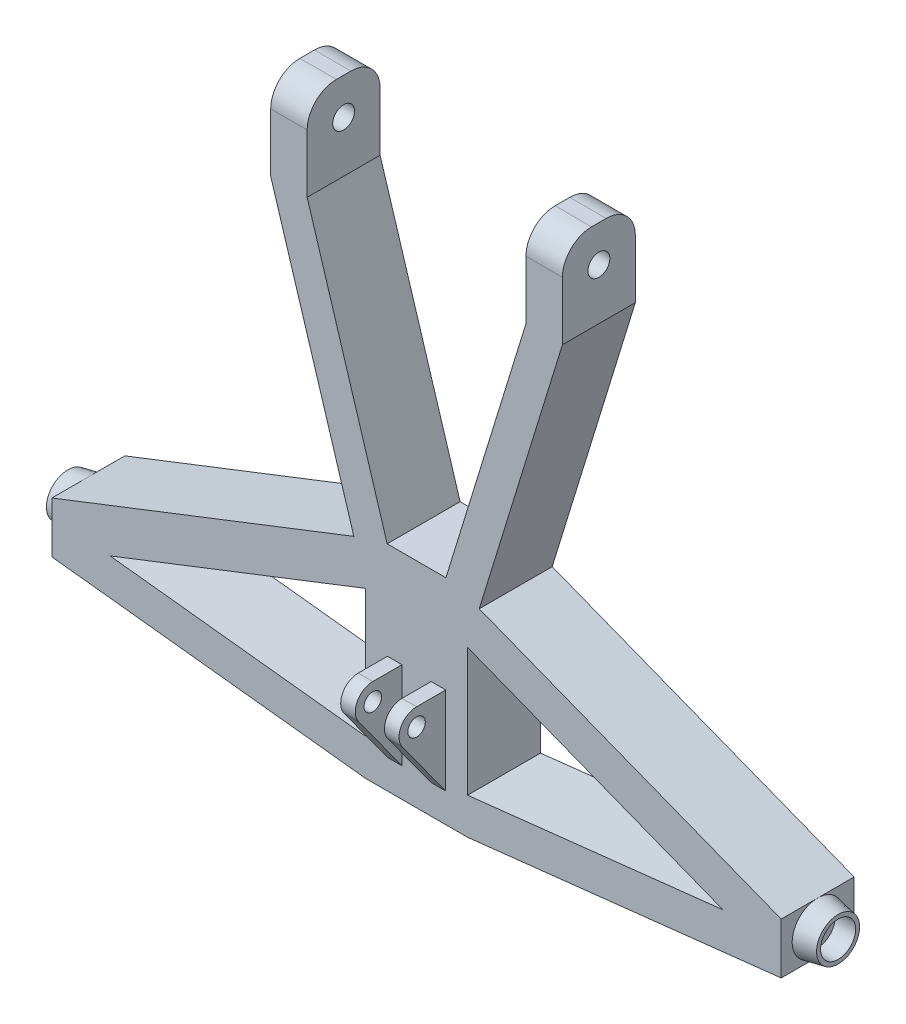
SolidWorks part; units mm, degrees
material "1060-H14"
ref_plane "Front Plane" through (0, 0, 0) normal (0, 0, 1) x (1, 0, 0)
ref_plane "Top Plane" through (0, 0, 0) normal (0, 1, 0) x (1, 0, 0)
ref_plane "Right Plane" through (0, 0, 0) normal (1, 0, 0) x (0, 0, -1)
sketch "Sketch1" plane through (0, 0, 0) normal (0, 0, 1) x (1, 0, 0)
  line L0 (100, 238.2726) -> (75, 238.2726)
  line L1 (-75, 238.2726) -> (-75, 178.2726)
  line L2 (-75, 178.2726) -> (0, -65.4485)
  line L3 (100, 178.2726) -> (100, 238.2726)
  line L4 (0, -146.6889) -> (100, 178.2726)
  line L5 (75, 178.2726) -> (0, -65.4485)
  line L6 (0, -146.6889) -> (-100, 178.2726)
  line L7 (0, -38.2835) -> (0, 78.4181) construction
  line L8 (-100, 178.2726) -> (-100, 238.2726)
  line L9 (-100, 238.2726) -> (-75, 238.2726)
  line L10 (75, 238.2726) -> (75, 178.2726)
  point P6 (0, 8.5727)
  dimension "D1" = 60
  dimension "D2" = 60
  dimension "D3" = 25
  dimension "D4" = 100
  dimension "D5" = 340
extrude "Boss-Extrude1" add sketch "Sketch1" along normal blind 50
sketch "Sketch2" plane through (-100, 0, 0) normal (-1, 0, 0) x (0, 0, 1)
  line L0 (50, 238.2726) -> (0, 238.2726) construction
  line L1 (0, 238.2726) -> (0, 178.2726) construction
  circle A0 centre (25, 213.2726) radius 7.5
  dimension "D1" = 15
  dimension "D2" = 25
  dimension "D3" = 25
extrude "Cut-Extrude1" cut sketch "Sketch2" against normal up to surface (200 mm away) contours A0 up to face at (100, 208.2726, 25)
fillet "Fillet1" radius 20 4 edges at (87.5, 238.2726, 50) (-87.5, 238.2726, 50) (-87.5, 238.2726, 0) (87.5, 238.2726, 0)
fillet "Fillet2" radius 20 1 edges at (0, -65.4485, 25)
sketch "Sketch4" plane through (0, 0, 50) normal (0, 0, 1) x (1, 0, 0)
  line L0 (0, 49.1752) -> (0, -207.4613) construction
  line L2 (-35, 0) -> (-35, -146.6889)
  line L3 (35, -146.6889) -> (-35, -146.6889)
  line L4 (-35, 0) -> (35, 0)
  line L5 (35, 0) -> (35, -146.6889)
  dimension "D2" = 35
extrude "Boss-Extrude2" add sketch "Sketch4" against normal up to surface (50 mm away) up to face at (0, 128.9739, 0)
sketch "Sketch7" plane through (0, 0, 50) normal (0, 0, 1) x (1, 0, 0)
  line L0 (0, 58.9331) -> (0, -339.9871) construction
  line L1 (-210.1113, -102.1604) -> (-35, -33.8889)
  line L2 (-35, -32.9524) -> (-35, -146.6889) construction
  line L3 (-35, -33.8889) -> (-35, -3.8889)
  line L4 (-250, -122.712) -> (-35, -146.6889)
  line L5 (-35, -146.6889) -> (-35, -121.6889)
  line L6 (-35, -121.6889) -> (-210.1113, -102.1604)
  line L7 (250, -87.712) -> (250, -122.712)
  line L8 (35, -3.8889) -> (250, -87.712)
  line L9 (-35, -3.8889) -> (-250, -87.712)
  line L10 (35, -121.6889) -> (210.1113, -102.1604)
  line L11 (-250, -87.712) -> (-250, -122.712)
  line L12 (35, -146.6889) -> (35, -121.6889)
  line L13 (250, -122.712) -> (35, -146.6889)
  line L14 (35, -33.8889) -> (35, -3.8889)
  line L15 (210.1113, -102.1604) -> (35, -33.8889)
  dimension "D1" = 250
  dimension "D2" = 35
  dimension "D3" = 25
  dimension "D4" = 30
extrude "Boss-Extrude4" add sketch "Sketch7" against normal up to surface (50 mm away) up to face at (0, 87.6356, 0)
shell "Shell13" thickness 3 removed face at (0, 47.6639, 0)
sketch "Sketch5" plane through (0, 0, 50) normal (0, 0, 1) x (1, 0, 0)
  line L0 (0, 20.8809) -> (0, -196.5712) construction
  line L1 (-20, -66.6889) -> (-10, -66.6889)
  line L2 (-20, -66.6889) -> (-20, -126.6889)
  line L3 (-20, -126.6889) -> (-10, -126.6889)
  line L4 (-10, -66.6889) -> (-10, -126.6889)
  line L5 (-35, -146.6889) -> (35, -146.6889) construction
  line L6 (10, -66.6889) -> (10, -126.6889)
  line L7 (20, -126.6889) -> (10, -126.6889)
  line L8 (20, -66.6889) -> (20, -126.6889)
  line L9 (20, -66.6889) -> (10, -66.6889)
  dimension "D1" = 10
  dimension "D2" = 60
  dimension "D3" = 20
  dimension "D4" = 10
extrude "Boss-Extrude3" add sketch "Sketch5" along normal blind 50
sketch "Sketch12" plane through (0, 0, 0) normal (0, 0, 1) x (1, 0, 0)
  line L0 (-32, -125.0421) -> (-32, -29.4994)
  line L1 (-32, -29.4994) -> (-222.5537, -103.7914)
  line L2 (-222.5537, -103.7914) -> (-32, -125.0421)
  line L3 (32, -125.0421) -> (32, -29.4994)
  line L4 (32, -29.4994) -> (222.5537, -103.7914)
  line L5 (222.5537, -103.7914) -> (32, -125.0421)
  line L18 (247, -89.7623) -> (39.2983, -8.7846)
  line L19 (247, -120.028) -> (247, -89.7623)
  line L20 (34.8332, -143.6889) -> (247, -120.028)
  line L21 (-34.8332, -143.6889) -> (34.8332, -143.6889)
  line L22 (-247, -120.028) -> (-34.8332, -143.6889)
  line L23 (-247, -89.7623) -> (-247, -120.028)
  line L24 (-39.2983, -8.7846) -> (-247, -89.7623)
  line L25 (-97, 178.7238) -> (-39.2983, -8.7846)
  line L26 (-97, 218.2726) -> (-97, 178.7238)
  line L27 (-78, 218.2726) -> (-97, 218.2726)
  line L28 (-78, 177.8215) -> (-78, 218.2726)
  line L29 (-22.356, -3) -> (-78, 177.8215)
  line L30 (22.356, -3) -> (-22.356, -3)
  line L31 (78, 177.8215) -> (22.356, -3)
  line L32 (78, 218.2726) -> (78, 177.8215)
  line L33 (97, 218.2726) -> (78, 218.2726)
  line L34 (97, 178.7238) -> (97, 218.2726)
  line L35 (39.2983, -8.7846) -> (97, 178.7238)
  line L36 (247, -89.7623) -> (39.2983, -8.7846)
  line L37 (247, -120.028) -> (247, -89.7623)
  line L38 (34.8332, -143.6889) -> (247, -120.028)
  line L39 (-34.8332, -143.6889) -> (34.8332, -143.6889)
  line L40 (-247, -120.028) -> (-34.8332, -143.6889)
  line L41 (-247, -89.7623) -> (-247, -120.028)
  line L42 (-39.2983, -8.7846) -> (-247, -89.7623)
  line L43 (-97, 178.7238) -> (-39.2983, -8.7846)
  line L44 (-97, 218.2726) -> (-97, 178.7238)
  line L45 (-78, 218.2726) -> (-97, 218.2726)
  line L46 (-78, 177.8215) -> (-78, 218.2726)
  line L47 (-22.356, -3) -> (-78, 177.8215)
  line L48 (22.356, -3) -> (-22.356, -3)
  line L49 (78, 177.8215) -> (22.356, -3)
  line L50 (78, 218.2726) -> (78, 177.8215)
  line L51 (97, 218.2726) -> (78, 218.2726)
  line L52 (97, 178.7238) -> (97, 218.2726)
  line L53 (39.2983, -8.7846) -> (97, 178.7238)
  dimension "D1" = 0
extrude "Boss-Extrude6" add sketch "Sketch12" along normal blind 3 separate body
sketch "Sketch6" plane through (20, 0, 0) normal (1, 0, 0) x (0, 0, -1)
  line L0 (-100, -66.6889) -> (-50, -66.6889) construction
  line L1 (-50, -126.6889) -> (-50, -66.6889) construction
  line L2 (-50, -126.6889) -> (-79.7129, -85.7359)
  line L3 (-50, -126.6889) -> (-50, -132.712)
  line L4 (-50, -121.6889) -> (-50, -33.8889) construction
  line L5 (-50, -132.712) -> (-106.0942, -132.712)
  line L6 (-106.0942, -132.712) -> (-106.0942, -60.4216)
  line L7 (-106.0942, -60.4216) -> (-70, -60.4216)
  line L8 (-70, -60.4216) -> (-70, -66.6889)
  circle A0 centre (-70, -78.6889) radius 6
  arc A1 (-70, -66.6889) -> (-79.7129, -85.7359) centre (-70, -78.6889) ccw
  dimension "D1" = 12
  dimension "D2" = 12
  dimension "D3" = 20
extrude "Cut-Extrude2" cut sketch "Sketch6" against normal blind 50
ref_plane "Plane1" through (0, 0, 25) normal (0, 0, -1) x (-1, 0, 0)
sketch "Sketch21" plane through (0, 0, 25) normal (0, 0, -1) x (-1, 0, 0)
  line L0 (-250, -105.212) -> (-264, -105.212) construction
  line L1 (-250, -122.712) -> (-250, -87.712) construction
  line L2 (-250, -93.212) -> (-264, -93.212)
  line L3 (-250, -87.712) -> (-264, -90.462)
  line L4 (-250, -87.712) -> (-250, -93.212)
  line L5 (-264, -90.462) -> (-264, -93.212)
  line L6 (-250, -90.462) -> (-264, -90.462) construction
  dimension "D1" = 24
  dimension "D2" = 14
revolve "Revolve1" add sketch "Sketch21" angle 360 about L0
mirror "Mirror1" about plane through (0, 0, 0) normal (1, 0, 0) of "Revolve1"
combine bodies "Combine1" operation type add bodies to combine 128 114
